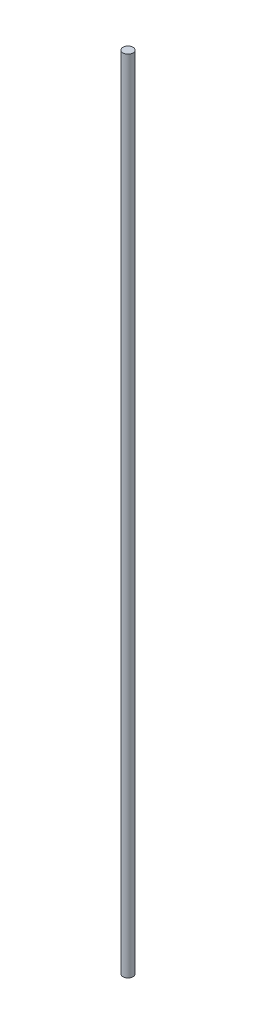
SolidWorks part; units mm, degrees
ref_plane "Front Plane" through (0, 0, 0) normal (0, 0, 1) x (1, 0, 0)
ref_plane "Top Plane" through (0, 0, 0) normal (0, 1, 0) x (1, 0, 0)
ref_plane "Right Plane" through (0, 0, 0) normal (1, 0, 0) x (0, 0, -1)
ref_axis "Axis X" through (-88.99, 0, 0) along (1, 0, 0)
ref_axis "Axis Y" through (0, 55, 0) along (0, -1, 0)
ref_axis "Axis Z" through (0, 0, -88.99) along (0, 0, 1)
sketch "Sketch1" plane through (0, 0, 0) normal (0, 1, 0) x (1, 0, 0)
  circle A0 centre (0, 0) radius 2.5
  dimension "D1" = 5
extrude "Boss-Extrude1" add sketch "Sketch1" along normal blind 400
